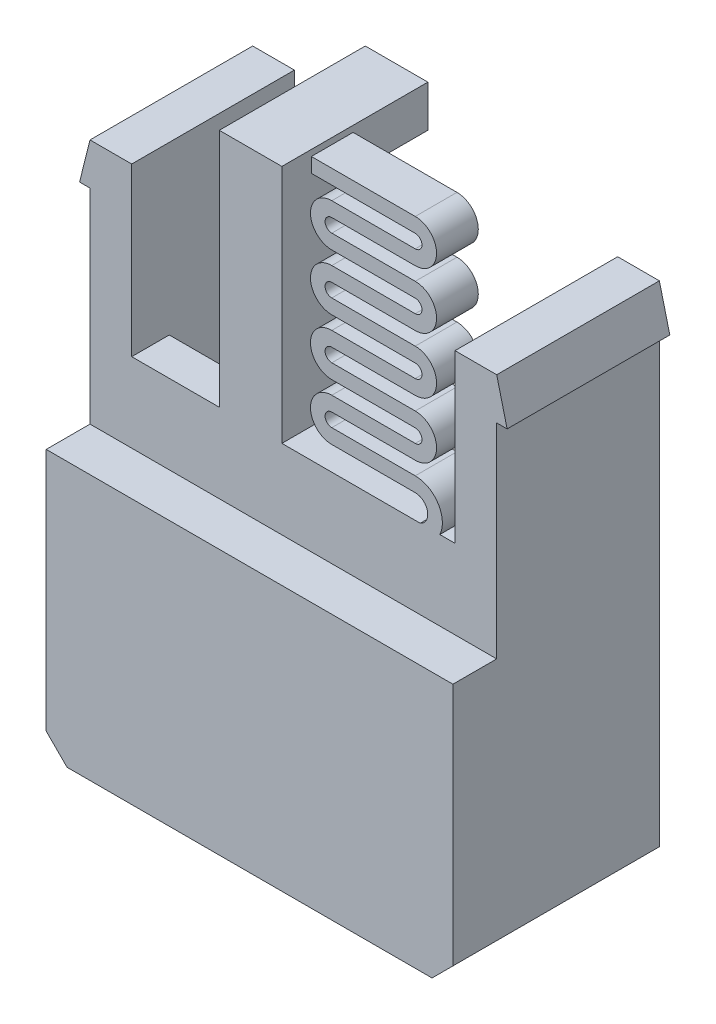
SolidWorks part; units mm, degrees
ref_plane "前视基准面" through (0, 0, 0) normal (0, 0, 1) x (1, 0, 0)
ref_plane "上视基准面" through (0, 0, 0) normal (0, 1, 0) x (1, 0, 0)
ref_plane "右视基准面" through (0, 0, 0) normal (1, 0, 0) x (0, 0, -1)
other "Configuration Table"
sketch "草图1" plane through (0, 0, 0) normal (0, 0, 1) x (1, 0, 0)
  line L0 (-63.9928, -19.7068) -> (-41.9928, -19.7068) construction
  line L1 (-62.7653, -7.0068) -> (-43.2653, -7.0068)
  line L2 (-62.7653, -7.0068) -> (-62.7653, -19.7068)
  line L3 (-62.7653, -19.7068) -> (-43.2653, -19.7068)
  line L4 (-43.2653, -7.0068) -> (-43.2653, -19.7068)
  dimension "D1" = 19.5
  dimension "D2" = 12.7
extrude "凸台-拉伸1" add sketch "草图1" along normal blind 2.1
sketch "草图2" plane through (0, 0, 0) normal (0, 0, -1) x (-1, 0, 0)
  line L1 (43.2653, -19.7068) -> (62.7653, -19.7068)
  line L2 (43.2653, -19.7068) -> (43.2653, 4.7932)
  line L3 (43.2653, 4.7932) -> (62.7653, 4.7932)
  line L4 (62.7653, -19.7068) -> (62.7653, 4.7932)
  dimension "D1" = 24.5
extrude "凸台-拉伸2" add sketch "草图2" along normal blind 7.8
sketch "草图3" plane through (0, 4.7932, 0) normal (0, 1, 0) x (1, 0, 0)
  line L0 (-62.7653, 7.8) -> (-43.2653, 7.8) construction
  line L1 (-60.7653, 7.8) -> (-45.2653, 7.8)
  line L2 (-60.7653, 7.8) -> (-60.7653, 1.8)
  line L3 (-60.7653, 1.8) -> (-45.2653, 1.8)
  line L4 (-45.2653, 7.8) -> (-45.2653, 1.8)
  line L5 (-62.7653, 7.8) -> (-62.7653, 0) construction
  line L6 (-43.2653, 7.8) -> (-43.2653, 0) construction
  dimension "D1" = 2
  dimension "D2" = 2
  dimension "D3" = 6
extrude "切除-拉伸1" cut sketch "草图3" against normal blind 23
sketch "草图4" plane through (0, 0, 0) normal (0, 0, 1) x (1, 0, 0)
  line L1 (-60.7653, 4.7932) -> (-45.2653, 4.7932)
  line L2 (-60.7653, 4.7932) -> (-60.7653, -3.2068)
  line L3 (-60.7653, -3.2068) -> (-45.2653, -3.2068)
  line L4 (-45.2653, 4.7932) -> (-45.2653, -3.2068)
  dimension "D1" = 8
extrude "切除-拉伸2" cut sketch "草图4" against normal up to next
sketch "草图5" plane through (0, 0, -7.8) normal (0, 0, -1) x (-1, 0, 0)
  line L0 (62.7653, 4.7932) -> (63.2653, 2.7932)
  line L1 (63.2653, 2.7932) -> (62.7653, 2.7932)
  line L2 (62.7653, -19.7068) -> (62.7653, 4.7932) construction
  line L3 (62.7653, 2.7932) -> (62.7653, 4.7932)
  line L4 (43.2653, 4.7932) -> (42.7653, 2.7932)
  line L5 (42.7653, 2.7932) -> (43.2653, 2.7932)
  line L6 (43.2653, 4.7932) -> (43.2653, -19.7068) construction
  line L7 (43.2653, 2.7932) -> (43.2653, 4.7932)
  dimension "D1" = 2
  dimension "D2" = 0.5
extrude "凸台-拉伸4" add sketch "草图5" against normal up to surface (7.8 mm away) up to face at (-53.0153, -0.1568, 0)
sketch "草图7" plane through (0, 0, 0) normal (0, 0, 1) x (1, 0, 0)
  line L0 (-47.1711, -1.7068) -> (-51.1711, -1.7068) construction
  line L1 (-60.7653, -3.2068) -> (-45.2653, -3.2068) construction
  line L2 (-47.1711, -0.3606) -> (-51.1711, -0.3606) construction
  line L3 (-47.1711, 0.9857) -> (-51.1711, 0.9857) construction
  line L4 (-47.1711, 2.3319) -> (-51.1711, 2.3319) construction
  line L5 (-47.1711, 3.6782) -> (-51.1711, 3.6782) construction
  line L6 (-47.1711, 5.0244) -> (-51.1711, 5.0244) construction
  line L7 (-47.1711, 6.3707) -> (-51.1711, 6.3707) construction
  line L8 (-47.1711, 7.7169) -> (-51.1711, 7.7169) construction
  line L9 (-47.1711, 9.0632) -> (-51.1711, 9.0632) construction
  line L10 (-47.1711, -1.3568) -> (-51.1711, -1.3568)
  line L11 (-47.1711, -0.7106) -> (-51.1711, -0.7106)
  line L12 (-47.1711, 1.3357) -> (-51.1711, 1.3357)
  line L13 (-47.1711, 1.9819) -> (-51.1711, 1.9819)
  line L14 (-47.1711, 4.0282) -> (-51.1711, 4.0282)
  line L15 (-47.1711, 4.6744) -> (-51.1711, 4.6744)
  line L16 (-47.1711, 6.7207) -> (-51.1711, 6.7207)
  line L17 (-47.1711, 7.3669) -> (-51.1711, 7.3669)
  line L18 (-47.1711, 9.4132) -> (-52.1509, 9.4132)
  line L19 (-47.1711, -2.0568) -> (-51.1711, -2.0568)
  line L20 (-47.1711, -0.0106) -> (-51.1711, -0.0106)
  line L21 (-47.1711, 0.6357) -> (-51.1711, 0.6357)
  line L22 (-47.1711, 2.6819) -> (-51.1711, 2.6819)
  line L23 (-47.1711, 3.3282) -> (-51.1711, 3.3282)
  line L24 (-47.1711, 5.3744) -> (-51.1711, 5.3744)
  line L25 (-47.1711, 6.0207) -> (-51.1711, 6.0207)
  line L26 (-47.1711, 8.0669) -> (-51.1711, 8.0669)
  line L27 (-47.1711, 8.7132) -> (-52.1509, 8.7132)
  line L28 (-47.1711, 9.0632) -> (-51.1407, 9.0632) construction
  line L29 (-47.1711, 8.7132) -> (-51.1407, 8.7132) construction
  line L30 (-47.1711, 9.4132) -> (-51.1407, 9.4132) construction
  line L31 (-72.3676, 9.4132) -> (-44.6127, 9.4132) construction
  line L32 (-52.1509, 9.4132) -> (-52.1509, 8.7132)
  line L33 (-46.9314, -3.2068) -> (-47.3969, -3.9371)
  arc A0 (-47.1711, -1.7068) -> (-46.3965, -3.2068) centre (-47.1711, -2.6568) cw construction
  arc A1 (-51.1711, -0.3606) -> (-51.1711, -1.7068) centre (-51.1711, -1.0337) ccw construction
  arc A2 (-47.1711, -0.3606) -> (-47.1711, 0.9857) centre (-47.1711, 0.3125) ccw construction
  arc A3 (-51.1711, 0.9857) -> (-51.1711, 2.3319) centre (-51.1711, 1.6588) cw construction
  arc A4 (-47.1711, 2.3319) -> (-47.1711, 3.6782) centre (-47.1711, 3.005) ccw construction
  arc A5 (-51.1711, 3.6782) -> (-51.1711, 5.0244) centre (-51.1711, 4.3513) cw construction
  arc A6 (-47.1711, 5.0244) -> (-47.1711, 6.3707) centre (-47.1711, 5.6975) ccw construction
  arc A7 (-51.1711, 6.3707) -> (-51.1711, 7.7169) centre (-51.1711, 7.0438) cw construction
  arc A8 (-47.1711, 7.7169) -> (-47.1711, 9.0632) centre (-47.1711, 8.39) ccw construction
  arc A9 (-47.1711, -1.3568) -> (-47.3969, -3.9371) centre (-47.1711, -2.6568) cw
  arc A10 (-51.1711, -0.7106) -> (-51.1711, -1.3568) centre (-51.1711, -1.0337) ccw
  arc A11 (-47.1711, -0.7106) -> (-47.1711, 1.3357) centre (-47.1711, 0.3125) ccw
  arc A12 (-51.1711, 1.3357) -> (-51.1711, 1.9819) centre (-51.1711, 1.6588) cw
  arc A13 (-47.1711, 1.9819) -> (-47.1711, 4.0282) centre (-47.1711, 3.005) ccw
  arc A14 (-51.1711, 4.0282) -> (-51.1711, 4.6744) centre (-51.1711, 4.3513) cw
  arc A15 (-47.1711, 4.6744) -> (-47.1711, 6.7207) centre (-47.1711, 5.6975) ccw
  arc A16 (-51.1711, 6.7207) -> (-51.1711, 7.3669) centre (-51.1711, 7.0438) cw
  arc A17 (-47.1711, 7.3669) -> (-47.1711, 9.4132) centre (-47.1711, 8.39) ccw
  arc A18 (-47.1711, -2.0568) -> (-46.9314, -3.2068) centre (-47.1711, -2.6568) cw
  arc A19 (-51.1711, -0.0106) -> (-51.1711, -2.0568) centre (-51.1711, -1.0337) ccw
  arc A20 (-47.1711, -0.0106) -> (-47.1711, 0.6357) centre (-47.1711, 0.3125) ccw
  arc A21 (-51.1711, 0.6357) -> (-51.1711, 2.6819) centre (-51.1711, 1.6588) cw
  arc A22 (-47.1711, 2.6819) -> (-47.1711, 3.3282) centre (-47.1711, 3.005) ccw
  arc A23 (-51.1711, 3.3282) -> (-51.1711, 5.3744) centre (-51.1711, 4.3513) cw
  arc A24 (-47.1711, 5.3744) -> (-47.1711, 6.0207) centre (-47.1711, 5.6975) ccw
  arc A25 (-51.1711, 6.0207) -> (-51.1711, 8.0669) centre (-51.1711, 7.0438) cw
  arc A26 (-47.1711, 8.0669) -> (-47.1711, 8.7132) centre (-47.1711, 8.39) ccw
  arc A27 (-47.1711, -1.7068) -> (-47.3361, -3.5924) centre (-47.1711, -2.6568) cw construction
  arc A28 (-47.1711, -2.0568) -> (-47.2753, -3.2477) centre (-47.1711, -2.6568) cw construction
  dimension "D1" = 4
  dimension "D2" = 1.5
  dimension "D4" = 0.35
  dimension "D5" = 0.35
  dimension "D3" = 9
extrude "凸台-拉伸5" add sketch "草图7" against normal blind 2
sketch "草图8" plane through (0, -3.2068, 0) normal (0, 1, 0) x (1, 0, 0)
  line L0 (-60.7653, 0) -> (-46.9314, 0) construction
  line L1 (-56.5653, 0) -> (-53.5653, 0)
  line L2 (-56.5653, 0) -> (-56.5653, 3)
  line L3 (-56.5653, 3) -> (-53.5653, 3)
  line L4 (-53.5653, 0) -> (-53.5653, 3)
  line L5 (-60.7653, 1.8) -> (-60.7653, 0) construction
  dimension "D1" = 4.2
  dimension "D2" = 3
  dimension "D3" = 3
extrude "凸台-拉伸6" add sketch "草图8" along normal blind 11.5 and the other way blind 4
sketch "草图9" plane through (0, 0, -3) normal (0, 0, -1) x (-1, 0, 0)
  line L0 (56.5653, -7.2068) -> (56.5653, 8.2932) construction
  line L1 (53.5653, 8.2932) -> (56.5653, 8.2932)
  line L2 (53.5653, 8.2932) -> (53.5653, 6.2932)
  line L3 (53.5653, 6.2932) -> (56.5653, 6.2932)
  line L4 (56.5653, 8.2932) -> (56.5653, 6.2932)
  dimension "D1" = 2
extrude "凸台-拉伸7" add sketch "草图9" along normal blind 4
chamfer "倒角1" distance 1 angle 45 2 edges at (-62.7653, -19.7068, -2.85) (-43.2653, -19.7068, -2.85)
